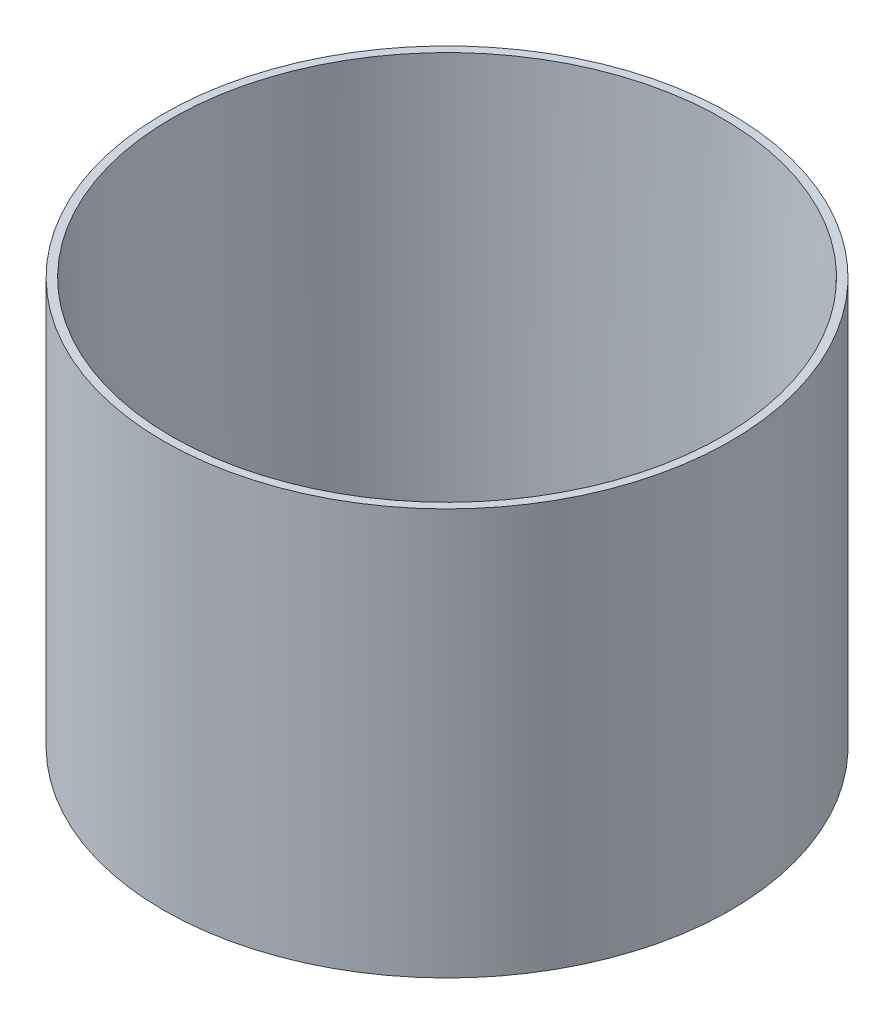
SolidWorks part; units mm, degrees
ref_plane "Front" through (0, 0, 0) normal (0, 0, 1) x (1, 0, 0)
ref_plane "Top" through (0, 0, 0) normal (0, 1, 0) x (1, 0, 0)
ref_plane "Right" through (0, 0, 0) normal (1, 0, 0) x (0, 0, -1)
sketch "Sketch1" plane through (0, 0, 0) normal (0, 1, 0) x (1, 0, 0)
  circle A0 centre (0, 0) radius 17.45
  circle A1 centre (0, 0) radius 16.25
  dimension "D1" = 32.5
  dimension "D2" = 34.9
extrude "Boss-Extrude1" add sketch "Sketch1" along normal blind 25
chamfer "Chamfer1" distance 0.7 distance2 25 1 edges at (0, 25, 16.25) first distance on face at (0, 25, 17.45)
